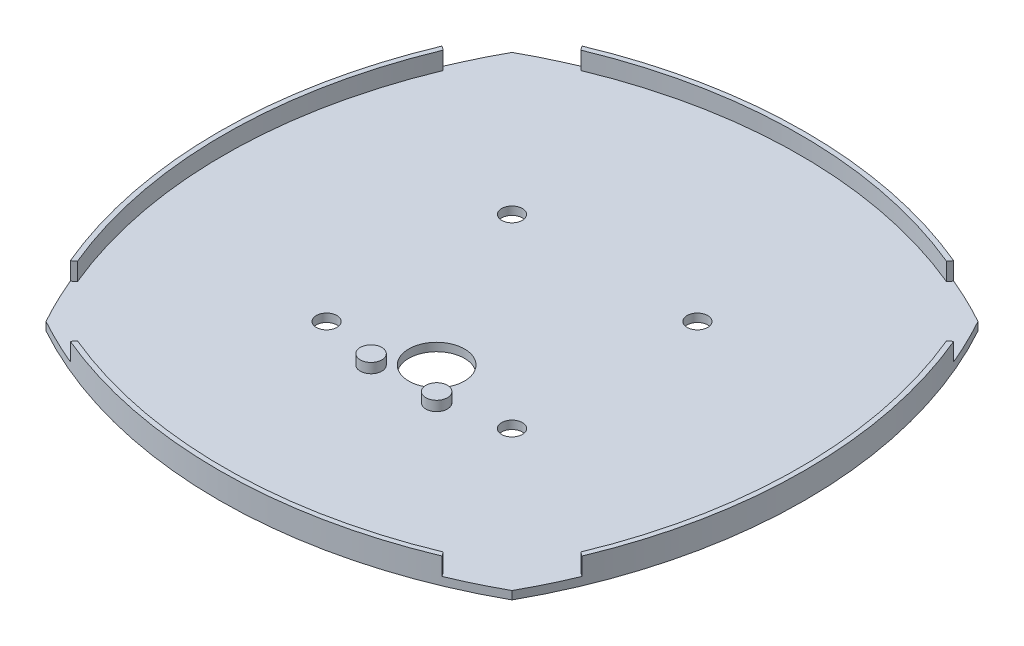
SolidWorks part; units mm, degrees
ref_plane "Front Plane" through (0, 0, 0) normal (0, 0, 1) x (1, 0, 0)
ref_plane "Top Plane" through (0, 0, 0) normal (0, 1, 0) x (1, 0, 0)
ref_plane "Right Plane" through (0, 0, 0) normal (1, 0, 0) x (0, 0, -1)
sketch "Sketch1" plane through (0, 0, 0) normal (0, 1, 0) x (1, 0, 0)
  line L0 (175.429, 389.4302) -> (225.429, 389.4742) construction
  dimension "D1" = 50
sketch "Sketch3" plane through (0, 0, 0) normal (0, 1, 0) x (1, 0, 0)
  line L2 (199.3319, -52.9004) -> (358.0133, -52.9004) construction
  line L3 (199.3319, -52.9004) -> (199.3319, 49.5555) construction
  arc A5 (130.4554, 15.9761) -> (130.4554, -121.7769) centre (256.8431, -52.9004) ccw construction
  arc A6 (268.2084, 15.9761) -> (130.4554, 15.9761) centre (199.3319, -110.4116) ccw construction
  arc A7 (268.2084, -121.7769) -> (268.2084, 15.9761) centre (141.8208, -52.9004) ccw construction
  arc A9 (130.4554, -121.7769) -> (268.2084, -121.7769) centre (199.3319, 4.6107) ccw construction
  arc A12 (270.4179, 18.1855) -> (128.246, 18.1855) centre (199.3319, -110.4116) ccw
  arc A14 (128.246, 18.1855) -> (128.246, -123.9864) centre (256.8431, -52.9004) ccw
  arc A15 (128.246, -123.9864) -> (270.4179, -123.9864) centre (199.3319, 4.6107) ccw
  arc A16 (270.4179, -123.9864) -> (270.4179, 18.1855) centre (141.8208, -52.9004) ccw
  point P0 (199.3319, -52.9004)
  point P15 (199.3319, -52.9004)
  dimension "D1" = 3
extrude "Boss-Extrude1" add sketch "Sketch3" along normal blind 2.5
sketch "Sketch5" plane through (0, 2.5, 0) normal (0, 1, 0) x (1, 0, 0)
  line L0 (141.8208, -52.9004) -> (256.8431, -52.9004) construction
  line L1 (199.3319, 4.6107) -> (199.3319, -110.4116) construction
  line L2 (122.535, -108.6966) -> (121.2877, -109.6029)
  line L3 (143.5357, -129.6973) -> (142.6295, -130.9447)
  line L4 (276.1288, 2.8958) -> (277.3762, 3.802)
  line L5 (255.1281, 23.8965) -> (256.0344, 25.1438)
  line L6 (276.1288, -108.6966) -> (277.3762, -109.6029)
  line L7 (255.1281, -129.6973) -> (256.0344, -130.9447)
  line L8 (122.535, 2.8958) -> (121.2877, 3.802)
  line L9 (143.5357, 23.8965) -> (142.6295, 25.1438)
  arc A8 (129.3502, -122.8821) -> (269.3136, -122.8821) centre (199.3319, 4.6107) ccw
  arc A9 (269.3136, -122.8821) -> (269.3136, 17.0813) centre (141.8208, -52.9004) ccw
  arc A10 (269.3136, 17.0813) -> (129.3502, 17.0813) centre (199.3319, -110.4116) ccw
  arc A11 (129.3502, 17.0813) -> (129.3502, -122.8821) centre (256.8431, -52.9004) ccw
  arc A12 (143.5357, -129.6973) -> (255.1281, -129.6973) centre (199.3319, 4.6107) ccw
  arc A13 (276.1288, -108.6966) -> (276.1288, 2.8958) centre (141.8208, -52.9004) ccw
  arc A14 (255.1281, 23.8965) -> (143.5357, 23.8965) centre (199.3319, -110.4116) ccw
  arc A15 (122.535, 2.8958) -> (122.535, -108.6966) centre (256.8431, -52.9004) ccw
  arc A21 (270.4179, 18.1855) -> (128.246, 18.1855) centre (199.3319, -110.4116) ccw
  arc A22 (270.4179, -123.9864) -> (270.4179, 18.1855) centre (141.8208, -52.9004) ccw
  arc A23 (128.246, -123.9864) -> (270.4179, -123.9864) centre (199.3319, 4.6107) ccw
  arc A24 (128.246, 18.1855) -> (128.246, -123.9864) centre (256.8431, -52.9004) ccw
  arc A25 (256.0344, 25.1438) -> (142.6295, 25.1438) centre (199.3319, -110.4116) ccw
  arc A26 (277.3762, -109.6029) -> (277.3762, 3.802) centre (141.8208, -52.9004) ccw
  arc A27 (142.6295, -130.9447) -> (256.0344, -130.9447) centre (199.3319, 4.6107) ccw
  arc A28 (121.2877, 3.802) -> (121.2877, -109.6029) centre (256.8431, -52.9004) ccw
  dimension "D2" = 36
  dimension "D3" = 36
  dimension "D4" = 36
  dimension "D5" = 36
  dimension "D6" = 36
  dimension "D7" = 36
  dimension "D8" = 36
  dimension "D9" = 36
  dimension "D1" = 1.5
  dimension "D10" = 0
extrude "Boss-Extrude2" add sketch "Sketch5" along normal blind 5.4
sketch "Sketch6" plane through (0, 2.5, 0) normal (0, 1, 0) x (1, 0, 0)
  line L0 (128.246, -123.9864) -> (270.4179, 18.1855) construction
  line L1 (128.246, 18.1855) -> (270.4179, -123.9864) construction
  line L2 (199.3319, -54.185) -> (199.3319, 43.8674) construction
  circle A1 centre (199.3319, -84.7202) radius 22.5
  point P12 (199.3319, -52.9004)
  dimension "D1" = 45
ref_plane "Plane1" through (0, 60, 0) normal (0, 1, 0) x (1, 0, 0)
sketch "Sketch11" plane through (0, 2.5, 0) normal (0, 1, 0) x (1, 0, 0)
  line L0 (128.246, -123.9864) -> (270.4179, 18.1855) construction
  line L1 (128.246, 18.1855) -> (270.4179, -123.9864) construction
  line L2 (199.3319, -50.7415) -> (199.3319, 48.5237) construction
  line L3 (199.3319, -52.9004) -> (293.7423, -52.9004) construction
  circle A0 centre (171.0477, -24.6162) radius 3.15
  circle A1 centre (227.6162, -24.6162) radius 3.15
  circle A2 centre (227.6162, -81.1847) radius 3.15
  circle A3 centre (171.0477, -81.1847) radius 3.15
  circle A4 centre (199.3319, -75.9004) radius 8.5
  point P11 (199.3319, -52.9004)
  point P24 (199.3319, -52.9004)
  dimension "D2" = 6.3
  dimension "D4" = 17
  dimension "D3" = 40
  dimension "D5" = 23
  dimension "D1" = 4
extrude "Cut-Extrude2" cut sketch "Sketch11" against normal through all both and the other way through all
sketch "Sketch13" plane through (0, 2.5, 0) normal (0, 1, 0) x (1, 0, 0)
  line L0 (199.3319, -74.6137) -> (199.3319, -39.6509) construction
  line L1 (199.3319, -75.9004) -> (212.0826, -75.9004) construction
  circle A5 centre (189.3319, -85.9004) radius 3.2895
  circle A6 centre (209.3319, -85.9004) radius 3.2895
  point P1 (199.3319, -75.9004)
  point P8 (0, 0)
  point P11 (0, 0)
  point P13 (192.9342, -83.1944)
  point P14 (199.3319, -75.9004)
  dimension "D1" = 10
  dimension "D2" = 10
extrude "Boss-Extrude3" add sketch "Sketch13" along normal blind 3
sketch "Sketch7" plane through (0, 60, 0) normal (0, 1, 0) x (1, 0, 0)
  line L0 (199.3319, -200054.185) -> (199.3319, 200043.8674) construction
  circle A0 centre (199.3319, -97.9702) radius 9
  dimension "D1" = 18
loft "Loft1" [suppressed] add profiles "Sketch7", "Sketch6"
sketch "Sketch8" [suppressed] plane through (0, 2.5, 0) normal (0, 1, 0) x (1, 0, 0)
  line L0 (199.3319, -97.9702) -> (199.3319, -52.584) construction
  line L1 (128.246, -123.9864) -> (270.4179, 18.1855) construction
  line L2 (128.246, 18.1855) -> (270.4179, -123.9864) construction
  circle A4 centre (199.3319, -97.9702) radius 9 construction
  circle A5 centre (199.3319, -75.9004) radius 8.5
  point P0 (199.3319, -97.9702)
  point P10 (199.3319, -52.9004)
  dimension "D1" = 17
  dimension "D2" = 23
sketch "Sketch9" [suppressed] plane through (0, 60, 0) normal (0, 1, 0) x (1, 0, 0)
  circle A0 centre (199.3319, -97.9702) radius 6
  dimension "D1" = 12
loft "Cut-Loft1" [suppressed] cut profiles "Sketch9", "Sketch8"
